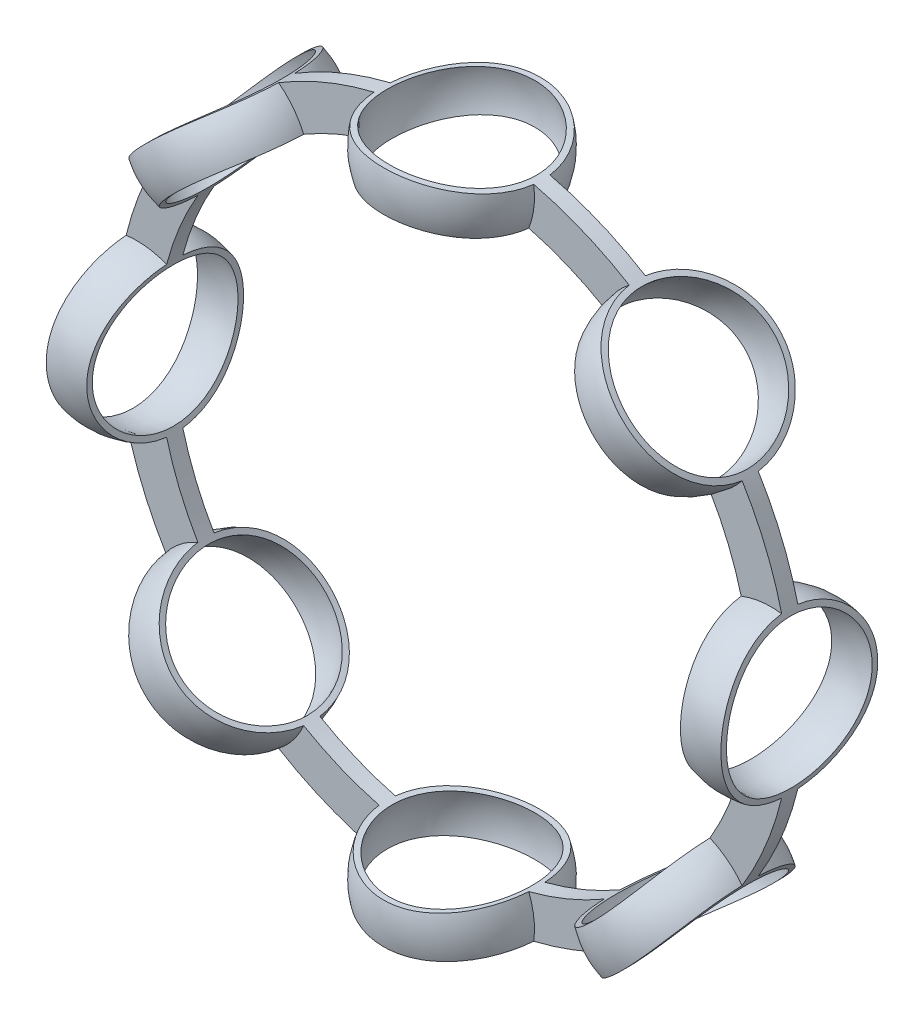
SolidWorks part; units mm, degrees
other "阵列(圆周)2"
material "锻制不锈钢"
ref_plane "前视基准面" through (0, 0, 0) normal (0, 0, 1) x (1, 0, 0)
ref_plane "上视基准面" through (0, 0, 0) normal (0, 1, 0) x (1, 0, 0)
ref_plane "右视基准面" through (0, 0, 0) normal (1, 0, 0) x (0, 0, -1)
sketch "草图1" plane through (0, 0, 0) normal (0, 0, 1) x (1, 0, 0)
  circle A0 centre (0, 0) radius 80
  dimension "D1" = 160
extrude "拉伸1" add sketch "草图1" along normal mid plane 3
sketch "草图4" plane through (0, 0, 0) normal (0, 1, 0) x (1, 0, 0)
  line L0 (58.75, 39.6642) -> (58.75, -39.6642) construction
  line L1 (58.75, 15) -> (58.75, -15)
  arc A0 (58.75, -15) -> (58.75, 15) centre (58.75, 0) ccw
  dimension "D1" = 30
  dimension "D2" = 58.75
revolve "旋转1" add sketch "草图4" angle 360 about L0
pattern_circular "阵列(圆周)1" count 8 over 360 about axis through (0, 0, 1.5) along (0, 0, -1) of "旋转1"
sketch "草图5" plane through (0, 0, 0) normal (0, 0, 1) x (1, 0, 0)
  circle A0 centre (0, 0) radius 62.5
  circle A1 centre (0, 0) radius 55
  dimension "D1" = 125
  dimension "D2" = 110
extrude "切除-拉伸1" cut sketch "草图5" against normal mid plane 70 flip side to cut
sketch "草图7" plane through (0, 0, 0) normal (0, 1, 0) x (1, 0, 0)
  line L0 (58.75, 25.5802) -> (58.75, -26.3487) construction
  line L1 (58.75, 14) -> (58.75, -14)
  arc A0 (58.75, -14) -> (58.75, 14) centre (58.75, 0) ccw
  dimension "D1" = 28
  dimension "D2" = 58.75
revolve "切除-旋转1" cut sketch "草图7" angle 360 about L0
pattern_circular "阵列(圆周)2" count 8 over 360 about axis through (0, 0, -35) along (0, 0, 1) of "切除-旋转1"
